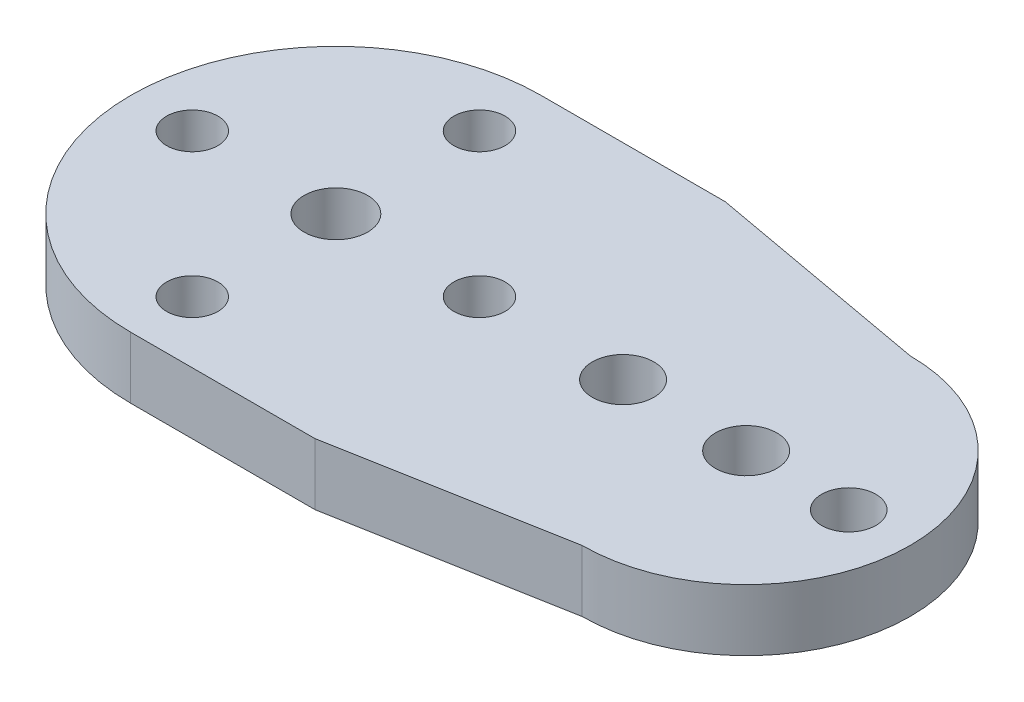
SolidWorks part; units mm, degrees
ref_plane "Front Plane" through (0, 0, 0) normal (0, 0, 1) x (1, 0, 0)
ref_plane "Top Plane" through (0, 0, 0) normal (0, 1, 0) x (1, 0, 0)
ref_plane "Right Plane" through (0, 0, 0) normal (1, 0, 0) x (0, 0, -1)
sketch "Sketch2" plane through (0, 0, 0) normal (0, 1, 0) x (1, 0, 0)
  line L1 (-71.018, 0) -> (-80, 0)
  line L3 (-71.018, 20) -> (-80, 20)
  line L5 (-80, 10) -> (-78.45, 10) construction
  line L6 (-80, 10) -> (-48, 10) construction
  line L13 (-71.018, 20) -> (-60, 18)
  line L14 (-71.018, 0) -> (-60, 2)
  arc A0 (-80, 20) -> (-80, 0) centre (-80, 10) ccw
  circle A3 centre (-80, 10) radius 1.55
  arc A5 (-60, 2) -> (-60, 18) centre (-60, 10) ccw
  circle A6 centre (-60, 10) radius 1.5
  dimension "D3" = 20
  dimension "D5" = 3
  dimension "D6" = 3.1
  dimension "D1" = 20
  dimension "D4" = 16
  dimension "D2" = 20
extrude "Boss-Extrude2" add sketch "Sketch2" along normal blind 3 contours L1 A0 L3 L13 A5 L14 | A3 | A6
sketch "Sketch3" plane through (0, 0, 0) normal (0, 1, 0) x (1, 0, 0)
  line L0 (-80, 20) -> (-80, 0) construction
  line L1 (-90, 10) -> (-70, 10) construction
  line L2 (-80, 10) -> (-52, 10) construction
  line L3 (-60, 18) -> (-60, 2) construction
  circle A0 centre (-80, 10) radius 10 construction
  circle A1 centre (-80, 17) radius 1.25
  circle A2 centre (-80, 3) radius 1.25
  circle A3 centre (-87, 10) radius 1.25
  circle A4 centre (-73, 10) radius 1.25
  arc A5 (-60, 2) -> (-60, 18) centre (-60, 10) ccw construction
  circle A6 centre (-66, 10) radius 1.5
  circle A7 centre (-55, 10) radius 1.3217
  dimension "D1" = 2.5
  dimension "D3" = 2.5
  dimension "D5" = 3
  dimension "D2" = 7
  dimension "D4" = 7
  dimension "D6" = 6
  dimension "6" = 5
extrude "Cut-Extrude1" cut sketch "Sketch3" along normal blind 10
